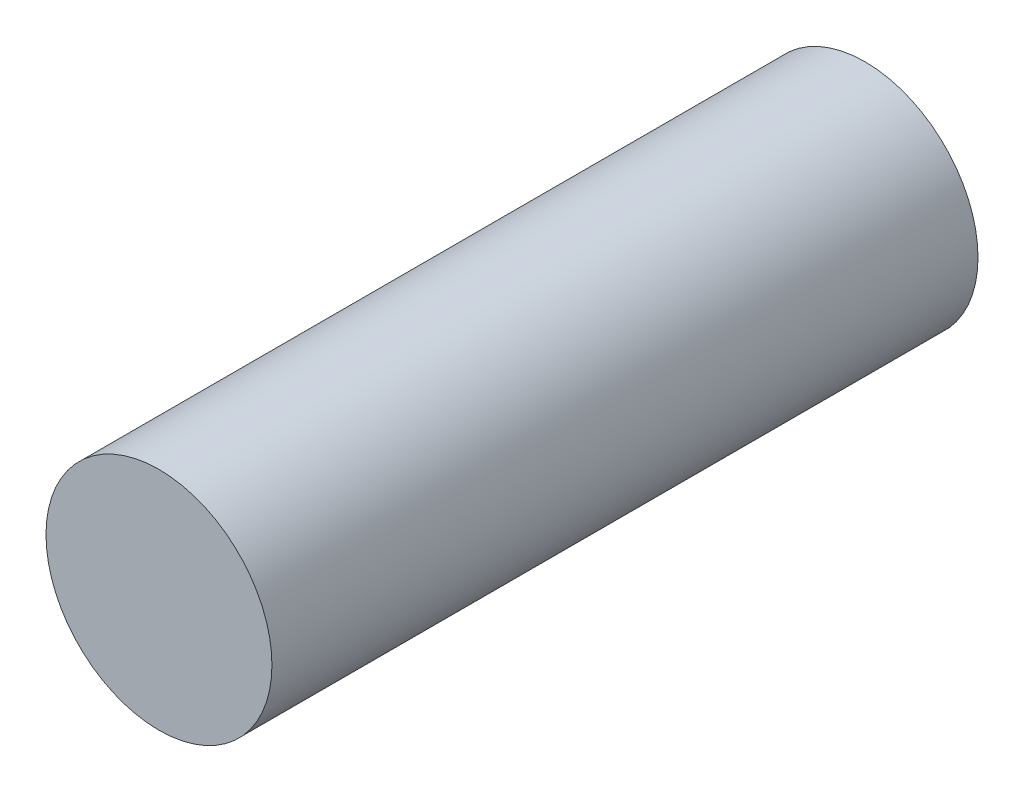
SolidWorks part; units mm, degrees
ref_plane "Front Plane" through (0, 0, 0) normal (0, 0, 1) x (1, 0, 0)
ref_plane "Top Plane" through (0, 0, 0) normal (0, 1, 0) x (1, 0, 0)
ref_plane "Right Plane" through (0, 0, 0) normal (1, 0, 0) x (0, 0, -1)
sketch "Croquis4" plane through (0, 0, 0) normal (0, 0, 1) x (1, 0, 0)
  circle A0 centre (0, 0) radius 2
  dimension "D1" = 4
extrude "Saliente-Extruir1" add sketch "Croquis4" along normal blind 10
sketch "Croquis5" plane through (0, 0, 0) normal (0, 0, -1) x (-1, 0, 0)
  circle A0 centre (0, 0) radius 2
extrude "Saliente-Extruir2" add sketch "Croquis5" along normal blind 2.5
